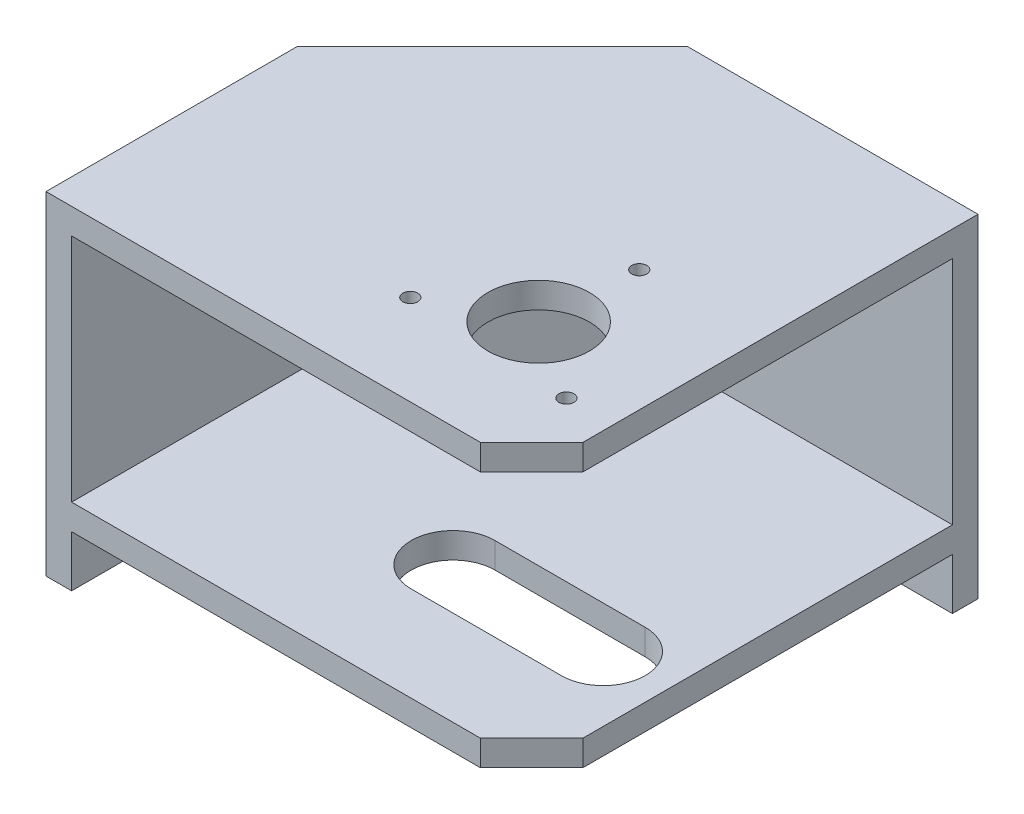
SolidWorks part; units mm, degrees
material "ABS"
ref_plane "Front Plane" through (0, 0, 0) normal (0, 0, 1) x (1, 0, 0)
ref_plane "Top Plane" through (0, 0, 0) normal (0, 1, 0) x (1, 0, 0)
ref_plane "Right Plane" through (0, 0, 0) normal (1, 0, 0) x (0, 0, -1)
sketch "Sketch1" plane through (0, 0, 0) normal (0, 1, 0) x (1, 0, 0)
  line L0 (-37.8071, 14.8204) -> (0.1929, 52.8204)
  line L1 (0.1929, 52.8204) -> (56.9846, 52.8204)
  line L2 (-37.8071, 14.8204) -> (-37.8071, -34.3004)
  line L3 (-37.8071, -34.3004) -> (46.9846, -34.3004)
  line L4 (56.9846, 52.8204) -> (56.9846, -24.3004)
  line L5 (46.9846, -34.3004) -> (56.9846, -24.3004)
  point P0 (-37.8071, 52.8204)
  point P1 (56.9846, -34.3004)
extrude "Boss-Extrude1" add sketch "Sketch1" along normal blind 5
sketch "Sketch2" plane through (0, 5, 0) normal (0, 1, 0) x (1, 0, 0)
  line L0 (44.3111, -7.6507) -> (15.0007, -7.6507) construction
  line L1 (44.3111, -15.8303) -> (15.0007, -15.8303)
  line L2 (44.3111, 0.529) -> (15.0007, 0.529)
  arc A1 (44.3111, -15.8303) -> (44.3111, 0.529) centre (44.3111, -7.6507) ccw
  arc A2 (15.0007, 0.529) -> (15.0007, -15.8303) centre (15.0007, -7.6507) ccw
  point P2 (29.6559, -7.6507)
extrude "Cut-Extrude1" cut sketch "Sketch2" against normal blind 10
sketch "Sketch3" plane through (0, 5, 0) normal (0, 1, 0) x (1, 0, 0)
  line L0 (0.1929, 52.8204) -> (56.9846, 52.8204)
  line L1 (56.9846, 52.8204) -> (0.1929, 52.8204) construction
  line L3 (-37.8071, 14.8204) -> (-37.8071, -34.3004) construction
  line L4 (-37.8071, -34.3004) -> (-37.8071, 14.8204)
  line L5 (-37.8071, 14.8204) -> (0.1929, 52.8204)
  line L6 (-37.8071, -34.3004) -> (-32.8071, -34.3004)
  line L7 (-37.8071, -34.3004) -> (46.9846, -34.3004) construction
  line L8 (-32.8071, -34.3004) -> (-32.8071, 12.7493)
  line L9 (-32.8071, 12.7493) -> (2.264, 47.8204)
  line L10 (2.264, 47.8204) -> (56.9846, 47.8204)
  line L11 (56.9846, -24.3004) -> (56.9846, 52.8204) construction
  line L12 (56.9846, 47.8204) -> (56.9846, 52.8204)
  dimension "D1" = 5
  dimension "D2" = 5
  dimension "D3" = 5
extrude "Boss-Extrude2" add sketch "Sketch3" along normal blind 50 and the other way blind 15
pattern_linear "LPattern1" count 2 spacing 50 along (0, 1, 0) of "Boss-Extrude1"
sketch "Sketch4" plane through (0, 55, 0) normal (0, 1, 0) x (1, 0, 0)
  circle A0 centre (32.2793, -8.2273) radius 9.9133
extrude "Cut-Extrude2" cut sketch "Sketch4" against normal blind 20
sketch "Sketch5" plane through (0, 55, 0) normal (0, 1, 0) x (1, 0, 0)
  circle A0 centre (33.2985, 10.3865) radius 1.4641
extrude "Cut-Extrude3" cut sketch "Sketch5" against normal blind 20
pattern_circular "CirPattern1" count 3 over 360 about axis through (32.2793, 55, 8.2273) along (0, 1, 0) of "Cut-Extrude3"
